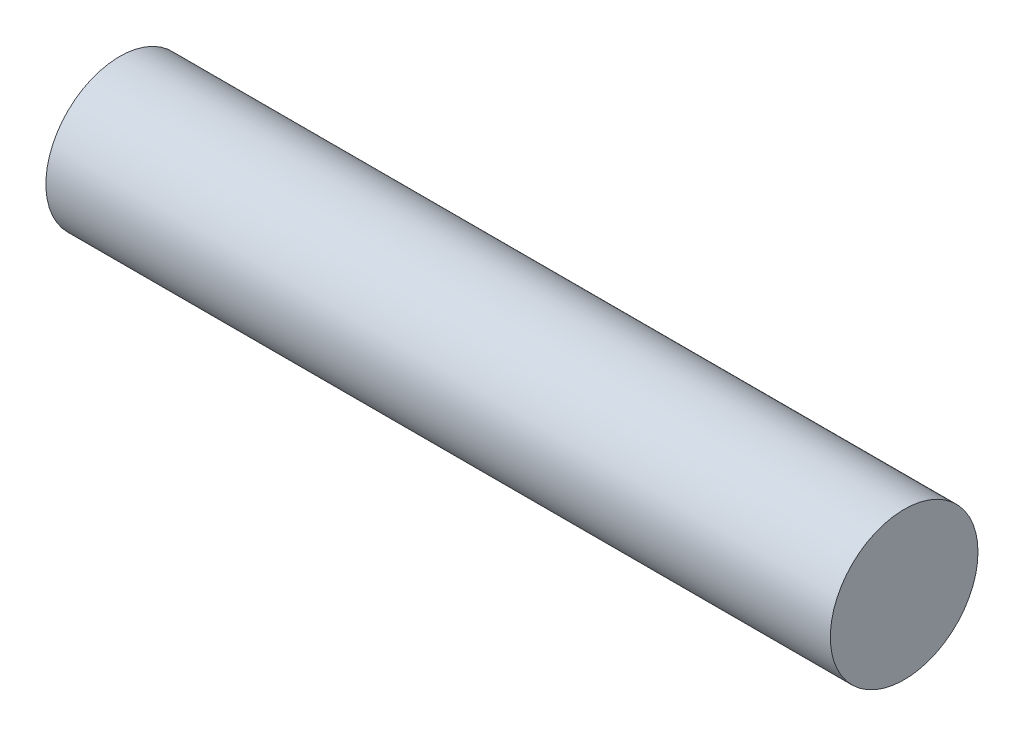
SolidWorks part; units mm, degrees
ref_plane "Front Plane" through (0, 0, 0) normal (0, 0, 1) x (1, 0, 0)
ref_plane "Top Plane" through (0, 0, 0) normal (0, 1, 0) x (1, 0, 0)
ref_plane "Right Plane" through (0, 0, 0) normal (1, 0, 0) x (0, 0, -1)
sketch "Sketch1" plane through (0, 0, 0) normal (1, 0, 0) x (0, 0, -1)
  circle A0 centre (0, 0) radius 80
extrude "FoamBody" add sketch "Sketch1" along normal mid plane 850 separate body
sketch "Sketch2" plane through (0, 0, 0) normal (0, 1, 0) x (1, 0, 0)
  line L1 (-343.5, -30) -> (-178.5, -30)
  line L2 (-343.5, -30) -> (-343.5, 30)
  line L3 (-343.5, 30) -> (-178.5, 30)
  line L4 (-178.5, -30) -> (-178.5, 30)
extrude "battery bay" cut sketch "Sketch2" against normal blind 60 from offset 10
sketch "Sketch3" plane through (0, 0, 0) normal (0, 1, 0) x (1, 0, 0)
  line L1 (-300, -40) -> (-150, -40)
  line L2 (-300, -40) -> (-300, 40)
  line L3 (-300, 40) -> (-150, 40)
  line L4 (-150, -40) -> (-150, 40)
extrude "Foam" cut sketch "Sketch3" along normal blind 35 from offset 10
sketch "Sketch4" plane through (0, 0, 0) normal (0, 1, 0) x (1, 0, 0)
  line L1 (-338.5, -24) -> (-183.5, -24)
  line L2 (-338.5, -24) -> (-338.5, 24)
  line L3 (-338.5, 24) -> (-183.5, 24)
  line L4 (-183.5, -24) -> (-183.5, 24)
extrude "Battery" add sketch "Sketch4" along normal blind 3 and the other way blind 47 separate body
sketch "Sketch5" plane through (0, 0, 0) normal (0, 1, 0) x (1, 0, 0)
  line L1 (-251, -16) -> (-199, -16)
  line L2 (-251, -16) -> (-251, 16)
  line L3 (-251, 16) -> (-199, 16)
  line L4 (-199, -16) -> (-199, 16)
extrude "FC" add sketch "Sketch5" along normal blind 17 from offset 13 separate body
